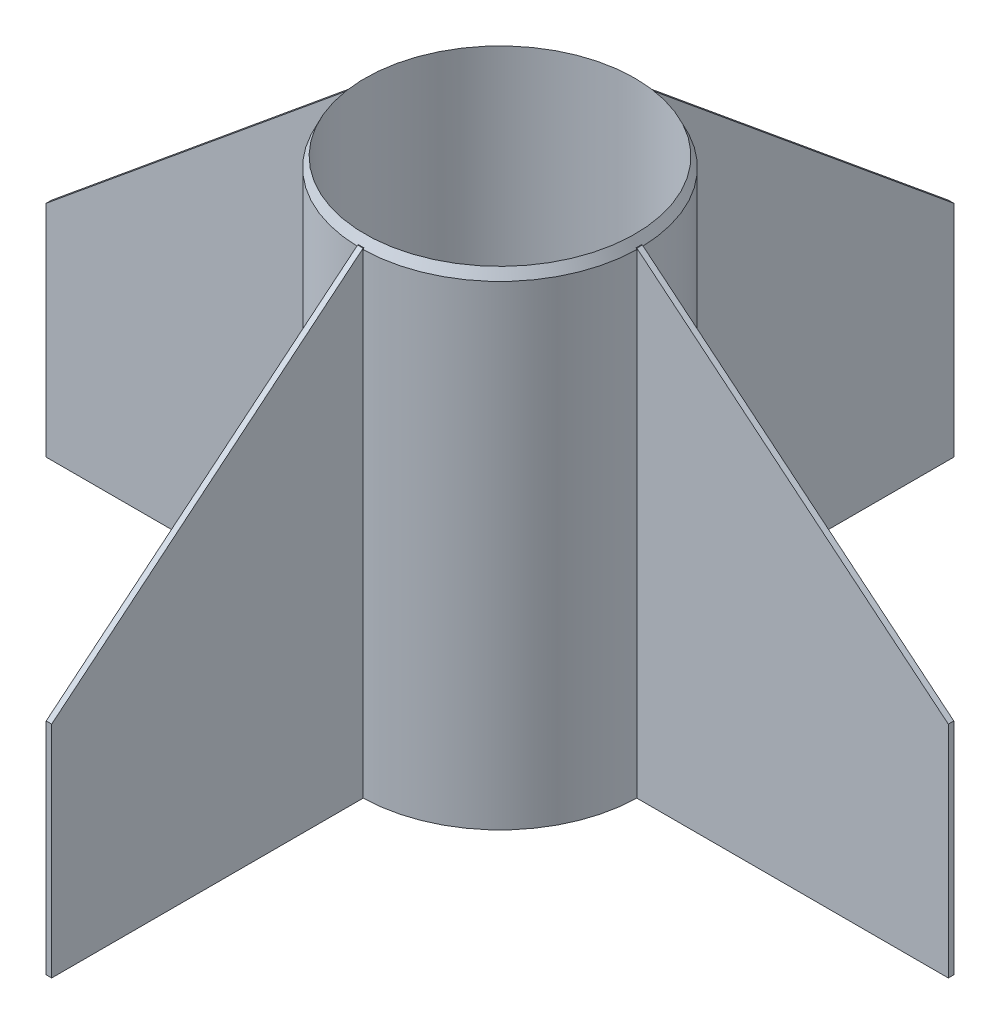
SolidWorks part; units mm, degrees
material "Commercially Pure grade 2 longitudinal (SS)"
ref_plane "Front Plane" through (0, 0, 0) normal (0, 0, 1) x (1, 0, 0)
ref_plane "Top Plane" through (0, 0, 0) normal (0, 1, 0) x (1, 0, 0)
ref_plane "Right Plane" through (0, 0, 0) normal (1, 0, 0) x (0, 0, -1)
sketch "Sketch1" plane through (0, 0, 0) normal (0, 1, 0) x (1, 0, 0)
  circle A0 centre (0, 0) radius 76.2
  circle A1 centre (0, 0) radius 73.7
  dimension "D1" = 152.4
  dimension "D2" = 147.4
extrude "Boss-Extrude1" add sketch "Sketch1" along normal blind 260
sketch "Sketch2" plane through (0, 0, 0) normal (0, 0, 1) x (1, 0, 0)
  line L0 (76.2, 0) -> (76.2, 260) construction
  line L1 (76.2, 0) -> (76.2, 260)
  line L2 (76.2, 0) -> (246.2, 0)
  line L3 (246.2, 0) -> (246.2, 120)
  line L4 (246.2, 120) -> (76.2, 260)
  dimension "D1" = 170
  dimension "D2" = 120
extrude "Boss-Extrude2" add sketch "Sketch2" along normal blind 1.5 and the other way blind 1.5 separate body
sketch "Sketch4" plane through (0, 0, 0) normal (0, 0, 1) x (1, 0, 0)
  line L0 (76.2, 260) -> (76.2, 0) construction
  line L1 (76.2, 260) -> (76.2, 0)
  line L2 (76.2, 260) -> (74.2, 260)
  line L3 (76.2, 260) -> (-76.2, 260) construction
  line L4 (74.2, 260) -> (74.2, 0)
  line L5 (-76.2, 0) -> (76.2, 0) construction
  line L6 (74.2, 0) -> (76.2, 0)
  point P2 (76.2, 130)
  dimension "D1" = 2
extrude "Boss-Extrude3" add sketch "Sketch4" along normal blind 1.5 and the other way blind 1.5
pattern_circular "CirPattern1" count 4 over 360 about axis through (0, 260, 0) along (0, -1, 0) of bodies 103
sketch "Sketch6" plane through (0, 260, 0) normal (0, 1, 0) x (1, 0, 0)
  arc A0 (76.1852, 1.5) -> (76.1852, -1.5) centre (0, 0) ccw construction
  circle A1 centre (0, 0) radius 73.7 construction
  arc A2 (76.1852, 1.5) -> (76.1852, -1.5) centre (0, 0) ccw
  circle A3 centre (0, 0) radius 73.7
  arc M2 (-1.5, 76.1852) -> (1.5, 76.1852) centre (0, 0) ccw
  circle M5 centre (0, 0) radius 73.7
extrude "Boss-Extrude4" add sketch "Sketch6" along normal blind 10 contours A2 M2 M5 region at (74.0447, 260, 0)
chamfer "Chamfer1" distance 5 angle 65 1 edges at (0, 270, 76.2) first distance on face at (0, 270, 73.7)
